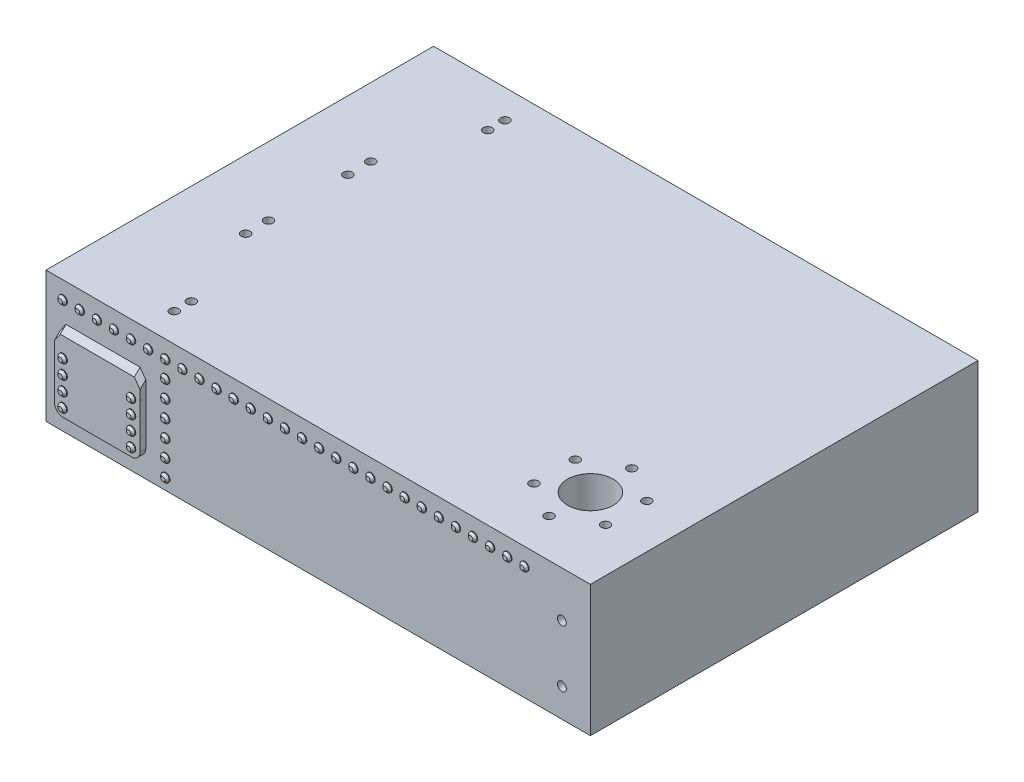
SolidWorks part; units mm, degrees
ref_plane "Front Plane" through (0, 0, 0) normal (0, 0, 1) x (1, 0, 0)
ref_plane "Top Plane" through (0, 0, 0) normal (0, 1, 0) x (1, 0, 0)
ref_plane "Right Plane" through (0, 0, 0) normal (1, 0, 0) x (0, 0, -1)
sketch "Sketch1" plane through (0, 0, 0) normal (0, 1, 0) x (1, 0, 0)
  line L1 (0, 0) -> (191, 0)
  line L2 (0, 0) -> (0, 136)
  line L3 (0, 136) -> (191, 136)
  line L4 (191, 0) -> (191, 136)
  dimension "D1" = 191
  dimension "D2" = 136
extrude "Boss-Extrude1" add sketch "Sketch1" along normal blind 46
sketch "Sketch3" plane through (0, 0, 0) normal (0, -1, 0) x (1, 0, 0)
  line L0 (0, -136) -> (0, 0) construction
  line L1 (5, -5) -> (186, -5)
  line L2 (5, -5) -> (5, -131)
  line L3 (5, -131) -> (186, -131)
  line L4 (186, -5) -> (186, -131)
  line L6 (191, -136) -> (0, -136) construction
  line L7 (191, 0) -> (191, -136) construction
  line L8 (0, 0) -> (191, 0) construction
  dimension "D1" = 5
  dimension "D2" = 5
  dimension "D3" = 5
  dimension "D4" = 5
extrude "Cut-Extrude1" cut sketch "Sketch3" against normal offset from surface (41 mm away) 5 contours L2 L3 L4 L1 up to face at (95.5, 46, -68)
ref_point "FrontLeft"
sketch "Sketch5" plane through (0, 0, -136) normal (0, 0, -1) x (-1, 0, 0)
  line L0 (-191, 46) -> (-119.5, 46)
  line L1 (-191, 46) -> (0, 46) construction
  line L2 (-119.5, 46) -> (-119.5, 0) construction
  line L3 (-191, 0) -> (0, 0) construction
  point P5 (-119.5, 23)
  dimension "D1" = 71.5
sketch "Sketch8" plane through (0, 0, 0) normal (0, 0, 1) x (1, 0, 0)
  line L1 (119.5, 46) -> (119.5, 0) construction
  line L2 (0, 46) -> (191, 46) construction
  line L3 (0, 0) -> (191, 0) construction
  point P0 (119.5, 23)
ref_point "SuspensionMountLeft"
ref_point "SuspensionMountRight"
sketch "Sketch9" plane through (0, 0, -136) normal (0, 0, -1) x (-1, 0, 0)
  line L0 (0, 46) -> (0, 0) construction
  line L1 (-5, 31) -> (-35, 31)
  line L2 (-5, 31) -> (-5, 6.2153)
  line L3 (-5, 6.2153) -> (-35, 6.2153)
  line L4 (-35, 31) -> (-35, 6.2153)
  line L5 (-191, 46) -> (0, 46) construction
  dimension "D1" = 5
  dimension "D2" = 15
  dimension "D3" = 30
extrude "Boss-Extrude2" add sketch "Sketch9" along normal blind 2
chamfer "Chamfer2" distance 2 angle 45 1 edges at (20, 31, -136)
fillet "Fillet1" radius 3 2 edges at (35, 6.2153, -137) (5, 6.2153, -137)
chamfer "Chamfer3" distance 2 angle 45 2 edges at (35, 32, -137) (5, 32, -137)
sketch "Sketch10" plane through (0, 0, 0) normal (0, 0, 1) x (1, 0, 0)
  line L4 (35, 31) -> (5, 31)
  line L5 (35, 6.2153) -> (35, 31)
  line L6 (5, 6.2153) -> (35, 6.2153)
  line L7 (5, 31) -> (5, 6.2153)
  line L8 (35, 31) -> (5, 31)
  line L9 (35, 6.2153) -> (35, 31)
  line L10 (5, 6.2153) -> (35, 6.2153)
  line L11 (5, 31) -> (5, 6.2153)
  dimension "D1" = 0
extrude "Boss-Extrude3" add sketch "Sketch10" along normal blind 2
chamfer "Chamfer4" distance 2 angle 45 1 edges at (20, 31, 0)
fillet "Fillet2" radius 3 2 edges at (35, 6.2153, 1) (5, 6.2153, 1)
chamfer "Chamfer5" distance 2 angle 45 2 edges at (35, 32, 1) (5, 32, 1)
sketch "Sketch23" plane through (0, 0, 2) normal (0, 0, 1) x (1, 0, 0)
  line L0 (8, 9.2153) -> (8, 31) construction
  line L1 (33, 31) -> (7, 31) construction
  line L2 (32, 9.2153) -> (32, 31) construction
  circle A0 centre (8, 9.2153) radius 1.5
  circle A1 centre (32, 9.2153) radius 1.5
  circle A2 centre (8, 14.2153) radius 1.5
  circle A3 centre (32, 14.2153) radius 1.5
  circle A4 centre (8, 19.2153) radius 1.5
  circle A5 centre (32, 19.2153) radius 1.5
  circle A6 centre (8, 24.2153) radius 1.5
  circle A7 centre (32, 24.2153) radius 1.5
  dimension "D1" = 3
  dimension "D2" = 3
  dimension "D3" = 4
extrude "Boss-Extrude8" add sketch "Sketch23" along normal blind 1 contours A4 | A2 | A0 | A1 | A3 | A5 | A7 | A6 region at (8, 9.2153, 2) region at (32, 9.2153, 2) region at (8, 14.2153, 2) region at (32, 14.2153, 2) region at (8, 19.2153, 2) region at (32, 19.2153, 2) region at (32, 24.2153, 2)
chamfer "Chamfer11" distance 0.75 angle 45 8 edges at (9.5, 24.2153, 3) (33.5, 9.2153, 3) (33.5, 14.2153, 3) (33.5, 19.2153, 3) (33.5, 24.2153, 3) (9.5, 9.2153, 3) (9.5, 14.2153, 3) (9.5, 19.2153, 3)
ref_plane "Plane1" through (0, 0, -68) normal (0, 0, 1) x (1, 0, 0)
mirror "Mirror1" about plane through (0, 0, -68) normal (0, 0, 1) of "Chamfer11", "Boss-Extrude8"
sketch "Sketch18" plane through (0, 41, 0) normal (0, -1, 0) x (1, 0, 0)
  line L1 (112.6585, -114) -> (114.6793, -117.5)
  line L2 (114.6793, -117.5) -> (118.7207, -117.5)
  line L3 (118.7207, -117.5) -> (120.7415, -114)
  line L4 (120.7415, -114) -> (118.7207, -110.5)
  line L5 (118.7207, -110.5) -> (114.6793, -110.5)
  line L6 (114.6793, -110.5) -> (112.6585, -114)
  line L7 (112.6585, -66) -> (114.6793, -69.5)
  line L8 (114.6793, -69.5) -> (118.7207, -69.5)
  line L9 (118.7207, -69.5) -> (120.7415, -66)
  line L10 (120.7415, -66) -> (118.7207, -62.5)
  line L11 (118.7207, -62.5) -> (114.6793, -62.5)
  line L12 (114.6793, -62.5) -> (112.6585, -66)
  line L13 (12.4585, -67) -> (14.4793, -70.5)
  line L14 (14.4793, -70.5) -> (18.5207, -70.5)
  line L15 (18.5207, -70.5) -> (20.5415, -67)
  line L16 (20.5415, -67) -> (18.5207, -63.5)
  line L17 (18.5207, -63.5) -> (14.4793, -63.5)
  line L18 (14.4793, -63.5) -> (12.4585, -67)
  line L19 (12.4585, -119.5) -> (14.4793, -123)
  line L20 (14.4793, -123) -> (18.5207, -123)
  line L21 (18.5207, -123) -> (20.5415, -119.5)
  line L22 (20.5415, -119.5) -> (18.5207, -116)
  line L23 (18.5207, -116) -> (14.4793, -116)
  line L24 (14.4793, -116) -> (12.4585, -119.5)
  circle A0 centre (116.7, -114) radius 3.5 construction
  circle A9 centre (116.7, -66) radius 3.5 construction
  circle A10 centre (16.5, -67) radius 3.5 construction
  circle A11 centre (16.5, -119.5) radius 3.5 construction
  point P41 (116.7, -114)
  point P42 (116.7, -66)
  point P43 (16.5, -67)
  point P44 (16.5, -119.5)
extrude "Boss-Extrude7" add sketch "Sketch18" along normal blind 14
sketch "Sketch19" plane through (0, 27, 0) normal (0, -1, 0) x (1, 0, 0)
  line L6 (112.6585, -66) -> (114.6793, -69.5)
  line L7 (114.6793, -69.5) -> (118.7207, -69.5)
  line L8 (118.7207, -69.5) -> (120.7415, -66)
  line L9 (120.7415, -66) -> (118.7207, -62.5)
  line L10 (118.7207, -62.5) -> (114.6793, -62.5)
  line L11 (114.6793, -62.5) -> (112.6585, -66)
  line L12 (112.6585, -66) -> (114.6793, -69.5)
  line L13 (114.6793, -69.5) -> (118.7207, -69.5)
  line L14 (118.7207, -69.5) -> (120.7415, -66)
  line L15 (120.7415, -66) -> (118.7207, -62.5)
  line L16 (118.7207, -62.5) -> (114.6793, -62.5)
  line L17 (114.6793, -62.5) -> (112.6585, -66)
  line L18 (120.7415, -114) -> (118.7207, -110.5)
  line L19 (118.7207, -110.5) -> (114.6793, -110.5)
  line L20 (114.6793, -110.5) -> (112.6585, -114)
  line L21 (112.6585, -114) -> (114.6793, -117.5)
  line L22 (114.6793, -117.5) -> (118.7207, -117.5)
  line L23 (118.7207, -117.5) -> (120.7415, -114)
  line L24 (120.7415, -114) -> (118.7207, -110.5)
  line L25 (118.7207, -110.5) -> (114.6793, -110.5)
  line L26 (114.6793, -110.5) -> (112.6585, -114)
  line L27 (112.6585, -114) -> (114.6793, -117.5)
  line L28 (114.6793, -117.5) -> (118.7207, -117.5)
  line L29 (118.7207, -117.5) -> (120.7415, -114)
  line L30 (12.4585, -119.5) -> (14.4793, -123)
  line L31 (14.4793, -123) -> (18.5207, -123)
  line L32 (18.5207, -123) -> (20.5415, -119.5)
  line L33 (20.5415, -119.5) -> (18.5207, -116)
  line L34 (18.5207, -116) -> (14.4793, -116)
  line L35 (14.4793, -116) -> (12.4585, -119.5)
  line L36 (12.4585, -119.5) -> (14.4793, -123)
  line L37 (14.4793, -123) -> (18.5207, -123)
  line L38 (18.5207, -123) -> (20.5415, -119.5)
  line L39 (20.5415, -119.5) -> (18.5207, -116)
  line L40 (18.5207, -116) -> (14.4793, -116)
  line L41 (14.4793, -116) -> (12.4585, -119.5)
  line L42 (18.5207, -63.5) -> (14.4793, -63.5)
  line L43 (20.5415, -67) -> (18.5207, -63.5)
  line L44 (18.5207, -70.5) -> (20.5415, -67)
  line L45 (14.4793, -70.5) -> (18.5207, -70.5)
  line L46 (12.4585, -67) -> (14.4793, -70.5)
  line L47 (14.4793, -63.5) -> (12.4585, -67)
  line L48 (18.5207, -63.5) -> (14.4793, -63.5)
  line L49 (20.5415, -67) -> (18.5207, -63.5)
  line L50 (18.5207, -70.5) -> (20.5415, -67)
  line L51 (14.4793, -70.5) -> (18.5207, -70.5)
  line L52 (12.4585, -67) -> (14.4793, -70.5)
  line L53 (14.4793, -63.5) -> (12.4585, -67)
  circle A0 centre (116.7, -66) radius 4.0415
  circle A1 centre (16.5, -67) radius 4.0415
  circle A2 centre (16.5, -119.5) radius 4.0415
  circle A3 centre (116.7, -114) radius 4.0415
  dimension "D1" = 0
  dimension "D2" = 0
  dimension "D3" = 0
  dimension "D4" = 0
hole_wizard "CSK for M2 Flat Head Machine Screw1" positions "Sketch21" profile "Sketch20" countersink size "M2" standard "ANSI Metric"
sketch "Sketch21" plane through (0, 27, 0) normal (0, -1, 0) x (-1, 0, 0)
  point P0 (-116.7, 114)
  point P3 (-116.7, 66)
  point P6 (-16.5, 67)
  point P9 (-16.5, 119.5)
sketch "Sketch20" plane through (116.7, 27, -114) normal (1, 0, 0) x (0, 0, -1)
  line L0 (0, 0) -> (0, 13.6009)
  line L1 (0, 13.6009) -> (1, 13)
  line L2 (1, 13) -> (1, 0.4195)
  line L3 (1, 0.4195) -> (1.5, 0)
  line L5 (1.5, 0) -> (0, 0)
  line L6 (-1, 0.4195) -> (-1.5, 0) construction
  line L10 (0, 13.6009) -> (-1, 13) construction
  line L11 (0, -6.35) -> (0, 107.95) construction
  dimension "Hole Dia." = 2
  dimension "Hole Depth" = 13
  dimension "Near C'Sink Dia." = 3
  dimension "Near C'Sink Angle" = 100
  dimension "Drill Angle" = 118
sketch "Sketch22" plane through (0, 0, 0) normal (-1, 0, 0) x (0, 0, 1)
  line L0 (0, 46) -> (0, 0) construction
  line L1 (-10, 10) -> (-80, 10)
  line L2 (-10, 10) -> (-10, 38)
  line L3 (-10, 38) -> (-80, 38)
  line L4 (-80, 10) -> (-80, 38)
  line L5 (-136, 0) -> (0, 0) construction
  line L6 (-136, 46) -> (0, 46) construction
  dimension "D1" = 10
  dimension "D2" = 10
  dimension "D3" = 8
  dimension "D4" = 70
extrude "Cut-Extrude2" [suppressed] cut sketch "Sketch22" against normal up to next
chamfer "Chamfer10" [suppressed] distance 28 angle 45
fillet "Fillet3" [suppressed] radius 3
sketch "Sketch24" plane through (0, 0, 0) normal (0, 0, 1) x (1, 0, 0)
  line L0 (0, 40) -> (191, 40) construction
  line L1 (0, 46) -> (0, 0) construction
  line L2 (191, 46) -> (191, 0) construction
  line L3 (0, 46) -> (191, 46) construction
  circle A0 centre (6, 40) radius 1.5
  circle A1 centre (12, 40) radius 1.5
  circle A2 centre (18, 40) radius 1.5
  circle A3 centre (24, 40) radius 1.5
  circle A4 centre (30, 40) radius 1.5
  circle A5 centre (36, 40) radius 1.5
  circle A6 centre (42, 40) radius 1.5
  circle A7 centre (48, 40) radius 1.5
  circle A8 centre (54, 40) radius 1.5
  circle A9 centre (60, 40) radius 1.5
  circle A10 centre (66, 40) radius 1.5
  circle A11 centre (72, 40) radius 1.5
  circle A12 centre (78, 40) radius 1.5
  circle A13 centre (84, 40) radius 1.5
  circle A14 centre (90, 40) radius 1.5
  circle A15 centre (96, 40) radius 1.5
  circle A16 centre (102, 40) radius 1.5
  circle A17 centre (108, 40) radius 1.5
  circle A18 centre (114, 40) radius 1.5
  circle A19 centre (120, 40) radius 1.5
  circle A20 centre (126, 40) radius 1.5
  circle A21 centre (132, 40) radius 1.5
  circle A22 centre (138, 40) radius 1.5
  circle A23 centre (144, 40) radius 1.5
  circle A24 centre (150, 40) radius 1.5
  circle A25 centre (156, 40) radius 1.5
  circle A26 centre (162, 40) radius 1.5
  circle A27 centre (168, 40) radius 1.5
  circle A28 centre (42, 34) radius 1.5
  circle A29 centre (42, 28) radius 1.5
  circle A30 centre (42, 22) radius 1.5
  circle A31 centre (42, 16) radius 1.5
  circle A32 centre (42, 10) radius 1.5
  circle A33 centre (42, 4) radius 1.5
  dimension "D2" = 3
  dimension "D1" = 6
  dimension "D3" = 6
  dimension "D4" = 28
  dimension "D5" = 7
extrude "Boss-Extrude9" add sketch "Sketch24" along normal blind 1
chamfer "Chamfer12" distance 0.75 angle 45 34 edges at (169.5, 40, 1) (163.5, 40, 1) (157.5, 40, 1) (151.5, 40, 1) (145.5, 40, 1) (139.5, 40, 1) (133.5, 40, 1) (127.5, 40, 1) (121.5, 40, 1) (115.5, 40, 1) (109.5, 40, 1) (103.5, 40, 1) (97.5, 40, 1) (91.5, 40, 1) (85.5, 40, 1) (79.5, 40, 1) (73.5, 40, 1) (67.5, 40, 1) (43.5, 4, 1) (43.5, 10, 1) (43.5, 16, 1) (43.5, 22, 1) (43.5, 28, 1) (43.5, 34, 1) (61.5, 40, 1) (55.5, 40, 1) (49.5, 40, 1) (43.5, 40, 1) (37.5, 40, 1) (31.5, 40, 1) (25.5, 40, 1) (19.5, 40, 1) (13.5, 40, 1) (7.5, 40, 1)
mirror "Mirror3" about plane through (0, 0, -68) normal (0, 0, 1) of "Chamfer12", "Boss-Extrude9"
sketch "Sketch25" plane through (0, 0, -131) normal (0, 0, 1) x (1, 0, 0)
  circle A0 centre (181, 30) radius 1.55 construction
  circle A1 centre (181, 10) radius 1.55 construction
  circle A2 centre (181, 30) radius 1.55
  circle A3 centre (181, 10) radius 1.55
extrude "Cut-Extrude3" cut sketch "Sketch25" against normal through all
sketch "Sketch26" plane through (0, 0, -5) normal (0, 0, -1) x (-1, 0, 0)
  circle A1 centre (-181, 10) radius 1.55
  circle A2 centre (-181, 10) radius 1.55
  circle A3 centre (-181, 30) radius 1.55
  circle A4 centre (-181, 30) radius 1.55
  dimension "D1" = 0
  dimension "D2" = 0
extrude "Cut-Extrude4" cut sketch "Sketch26" against normal through all
sketch "Sketch27" plane through (0, 46, 0) normal (0, 1, 0) x (1, 0, 0)
  line L0 (191, 0) -> (191, 136) construction
  line L1 (0, 0) -> (191, 0) construction
  circle A0 centre (163, 28) radius 1
  dimension "D1" = 2
  dimension "D2" = 28
  dimension "D3" = 28
sketch "Sketch28" plane through (0, 41, 0) normal (0, -1, 0) x (1, 0, 0)
  circle A0 centre (163, -13.5) radius 1.55 construction
  circle A1 centre (163, -28) radius 18
  circle A2 centre (163, -28) radius 18
  circle A3 centre (163, -28) radius 8
  circle A4 centre (163, -28) radius 8
  circle A5 centre (175.5574, -20.75) radius 1.55 construction
  circle A6 centre (175.5574, -35.25) radius 1.55 construction
  circle A7 centre (163, -42.5) radius 1.55 construction
  circle A8 centre (150.4426, -35.25) radius 1.55 construction
  circle A9 centre (150.4426, -20.75) radius 1.55 construction
  circle A10 centre (163, -13.5) radius 1.55
  circle A11 centre (175.5574, -20.75) radius 1.55
  circle A12 centre (175.5574, -35.25) radius 1.55
  circle A13 centre (163, -42.5) radius 1.55
  circle A14 centre (150.4426, -35.25) radius 1.55
  circle A15 centre (150.4426, -20.75) radius 1.55
  circle A17 centre (163, -28) radius 11
  circle A18 centre (163, -28) radius 11
  dimension "D1" = 0
  dimension "D2" = 0
  dimension "D3" = 0
extrude "Cut-Extrude5" cut sketch "Sketch28" against normal through all contours A13 | A12 | A11 | A10 | A15 | A14 region at (163, 41, -13.5) region at (175.5574, 41, -20.75) region at (175.5574, 41, -35.25) region at (163, 41, -42.5) region at (150.4426, 41, -35.25) region at (150.4426, 41, -20.75)
extrude "Cut-Extrude6" cut sketch "Sketch28<3>" against normal through all contours A4 region at (163, 41, -28)
sketch "Sketch28<3>" plane through (0, 41, 0) normal (0, -1, 0) x (1, 0, 0) same geometry as "Sketch28"
extrude "Boss-Extrude10" add sketch "Sketch28<4>" along normal blind 40 contours A18 A4 region at (152.3111, 41, -28)
sketch "Sketch28<4>" plane through (0, 41, 0) normal (0, -1, 0) x (1, 0, 0) same geometry as "Sketch28"
sketch "Sketch29" plane through (0, 1, 0) normal (0, -1, 0) x (1, 0, 0)
  line L0 (163, -28) -> (163, -43.0058) construction
  line L1 (163, -43.0058) -> (162, -43.0058)
  line L2 (163, -43.0058) -> (164, -43.0058)
  line L3 (164, -43.0058) -> (164, -13.0058)
  line L4 (164, -13.0058) -> (162, -13.0058)
  line L5 (162, -13.0058) -> (162, -43.0058)
  dimension "D2" = 1
  dimension "D1" = 1
  dimension "D3" = 30
extrude "Cut-Extrude7" cut sketch "Sketch29" against normal blind 20
ref_plane "Plane2" through (163, 46, -28) normal (0, 0, 1) x (1, 0, 0)
sketch "Sketch30" plane through (163, 46, -28) normal (0, 0, 1) x (1, 0, 0)
  line L0 (11, -5) -> (11, -46) construction
  line L1 (11, -45) -> (11, -5) construction
  line L2 (18, -5) -> (18, -46) construction
  line L3 (18, -5) -> (11, -25.5) construction
  line L4 (23, -5) -> (-158, -5)
  line L5 (-158, -5) -> (-158, -46)
  line L6 (-158, -46) -> (23, -46)
  line L7 (23, -46) -> (23, -5)
  line L8 (23, -5) -> (-158, -5)
  line L9 (-158, -5) -> (-158, -46)
  line L10 (-158, -46) -> (23, -46)
  line L11 (23, -46) -> (23, -5)
  line L12 (17, -7.9286) -> (12, -22.5714)
  line L13 (17, -7.9286) -> (17, -5)
  line L14 (17, -5) -> (17, -4.9)
  line L15 (12, -22.5714) -> (11, -22.5714)
  line L16 (11, -22.5714) -> (10.9, -22.5714)
  line L17 (10.9, -22.5714) -> (10.9, -4.9)
  line L18 (10.9, -4.9) -> (17, -4.9)
  dimension "D2" = 1
  dimension "D3" = 1
  dimension "D4" = 0.1
  dimension "D5" = 0.1
  dimension "D1" = 0
extrude "Boss-Extrude11" add sketch "Sketch30" along normal mid plane 3 contours L17 L16 L15 L12 L13 L8 region at (176.2325, 34.2396, -28)
ref_axis "Axis1" through (163, 46, -28) along (0, -1, 0)
pattern_circular "CirPattern1" count 6 over 360 about axis through (163, 46, -28) along (0, -1, 0) of "Boss-Extrude11"
chamfer "Chamfer13" distance 0.5 angle 45 2 edges at (174, 1, -28) (152, 1, -28)
sketch "Sketch31" plane through (0, 41, 0) normal (0, -1, 0) x (1, 0, 0)
  circle A0 centre (35, -16) radius 1.55 construction
  circle A1 centre (35, -10) radius 1.55 construction
  circle A2 centre (35, -126) radius 1.55 construction
  circle A3 centre (35, -120) radius 1.55 construction
  circle A4 centre (35, -16) radius 1.55
  circle A5 centre (35, -10) radius 1.55
  circle A6 centre (35, -126) radius 1.55
  circle A7 centre (35, -120) radius 1.55
extrude "Cut-Extrude8" cut sketch "Sketch31" against normal up to next
sketch "Sketch32" plane through (5, 0, 0) normal (1, 0, 0) x (0, 0, -1)
  circle A0 centre (125.5, 17.25) radius 1.55 construction
  circle A1 centre (10.5, 17.25) radius 1.55 construction
  circle A2 centre (125.5, 17.25) radius 1.55
  circle A3 centre (10.5, 17.25) radius 1.55
extrude "Cut-Extrude9" cut sketch "Sketch32" against normal up to next
sketch "Sketch34" plane through (5, 0, 0) normal (1, 0, 0) x (0, 0, -1)
  circle A0 centre (46.0692, 8) radius 1.55 construction
  circle A1 centre (89.9308, 8) radius 1.55 construction
  circle A2 centre (46.0692, 8) radius 1.55
  circle A3 centre (89.9308, 8) radius 1.55
extrude "Cut-Extrude10" cut sketch "Sketch34" against normal up to next
sketch "Sketch35" plane through (0, 41, 0) normal (0, -1, 0) x (1, 0, 0)
  circle A0 centre (24, -46.0692) radius 1.55 construction
  circle A1 centre (24, -54.0692) radius 1.55 construction
  circle A2 centre (24, -81.9308) radius 1.55 construction
  circle A3 centre (24, -89.9308) radius 1.55 construction
  circle A4 centre (24, -46.0692) radius 1.55
  circle A5 centre (24, -54.0692) radius 1.55
  circle A6 centre (24, -81.9308) radius 1.55
  circle A7 centre (24, -89.9308) radius 1.55
extrude "Cut-Extrude11" cut sketch "Sketch35" against normal up to next
sketch "Sketch36" plane through (0, 46, 0) normal (0, 1, 0) x (1, 0, 0)
  line L0 (191, 68) -> (85, 68) construction
  line L1 (191, 0) -> (191, 136) construction
  dimension "D1" = 106
